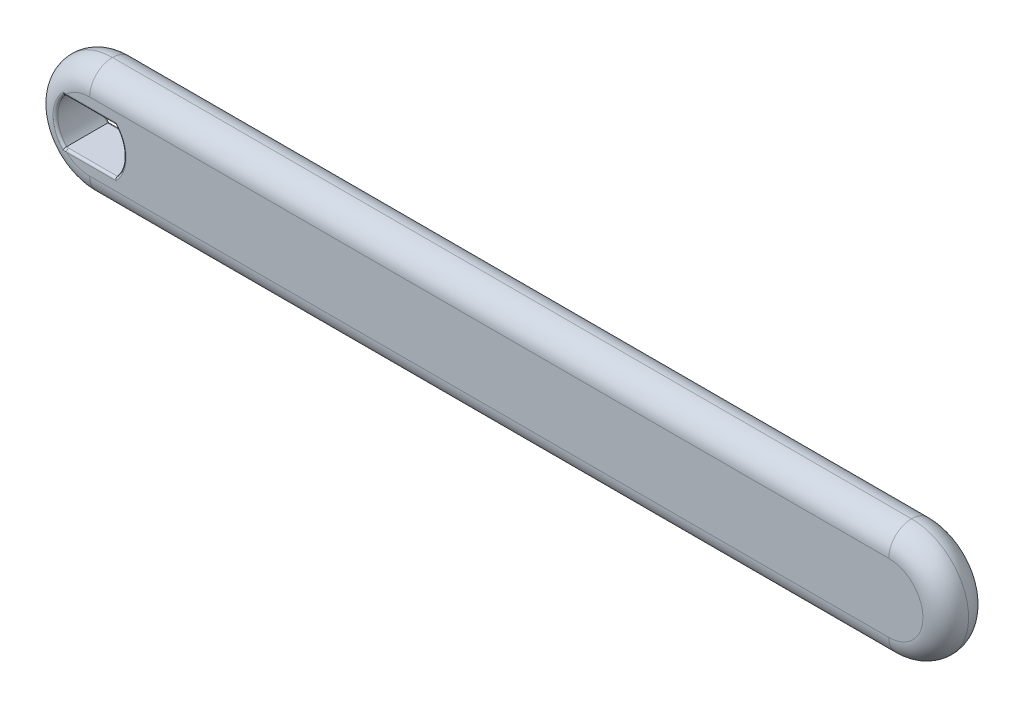
SolidWorks part; units mm, degrees
ref_plane "Front Plane" through (0, 0, 0) normal (0, 0, 1) x (1, 0, 0)
ref_plane "Top Plane" through (0, 0, 0) normal (0, 1, 0) x (1, 0, 0)
ref_plane "Right Plane" through (0, 0, 0) normal (1, 0, 0) x (0, 0, -1)
sketch "Sketch1" plane through (0, 0, 0) normal (0, 0, 1) x (1, 0, 0)
  line L0 (-12.5, 12.5) -> (187.5, -12.5) construction
  line L1 (-12.5, 12.5) -> (187.5, 12.5)
  line L2 (-12.5, 12.5) -> (-12.5, -12.5)
  line L3 (-12.5, -12.5) -> (187.5, -12.5)
  line L4 (187.5, 12.5) -> (187.5, -12.5)
  line L5 (0, 0) -> (87.5, 0) construction
  circle A0 centre (0, 0) radius 12.5
  circle A1 centre (175, 0) radius 12.5
  dimension "D1" = 200
  dimension "D2" = 25
extrude "Boss-Extrude1" add sketch "Sketch1" along normal blind 10 contours A0 L3 L4 L1 | A0 | A1 region at (87.5, 0, 0) region at (0, 0, 0) region at (175, 0, 0)
sketch "Sketch2" plane through (0, 0, 10) normal (0, 0, 1) x (1, 0, 0)
  line L0 (-5.5902, 5) -> (5.5902, 5)
  line L1 (0, 5) -> (0, -5) construction
  line L2 (5.5902, -5) -> (-5.5902, -5)
  circle A0 centre (0, 0) radius 7.5
  dimension "D1" = 15
  dimension "D2" = 10
extrude "Cut-Extrude1" cut sketch "Sketch2" against normal through all contours L0 L1 L2 A0 | L1 L0 A0 L2 region at (-3.4723, 0, 10) region at (3.4723, 0, 10)
fillet "Fillet3" radius 5 8 edges at (-12.5, 0, 10) (87.5, -12.5, 10) (187.5, 0, 10) (-12.5, 0, 0) (87.5, -12.5, 0) (187.5, 0, 0) (87.5, 12.5, 10) (87.5, 12.5, 0)
fillet "Fillet4" radius 0.5 8 edges at (0, -5, 10) (7.5, 0, 10) (0, 5, 10) (-7.5, 0, 10) (0, 5, 0) (7.5, 0, 0) (0, -5, 0) (-7.5, 0, 0)
